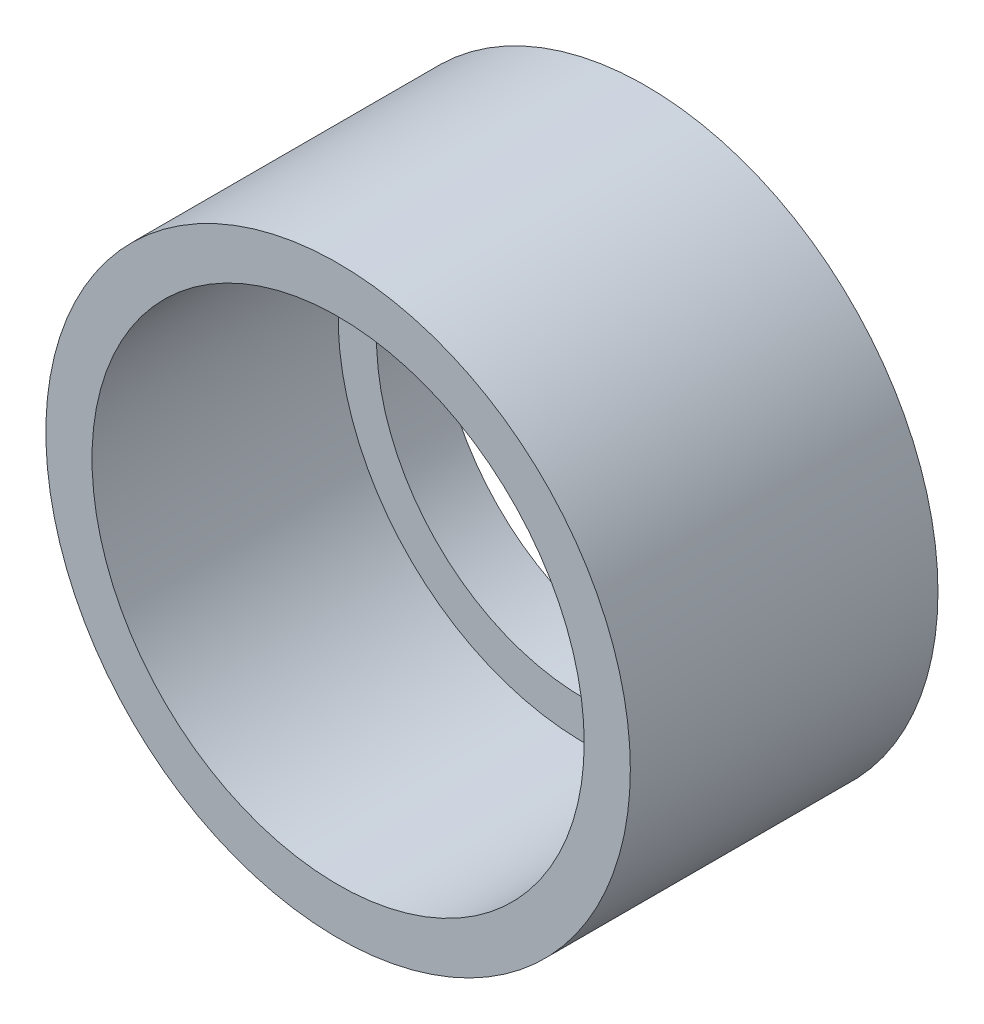
SolidWorks part; units mm, degrees
material "ABS"
ref_plane "Front Plane" through (0, 0, 0) normal (0, 0, 1) x (1, 0, 0)
ref_plane "Top Plane" through (0, 0, 0) normal (0, 1, 0) x (1, 0, 0)
ref_plane "Right Plane" through (0, 0, 0) normal (1, 0, 0) x (0, 0, -1)
sketch "Sketch1" plane through (0, 0, 0) normal (0, 0, 1) x (1, 0, 0)
  circle A0 centre (0, 0) radius 9.5
  circle A1 centre (0, 0) radius 8
  circle A2 centre (0, 0) radius 6.75
  dimension "D1" = 16
  dimension "D2" = 1.5
  dimension "D3" = 13.5
extrude "Boss-Extrude1" add sketch "Sketch1" along normal mid plane 10 contours A0 A1 region at (-9.2313, 0, 0)
extrude "Boss-Extrude2" add sketch "Sketch1<3>" along normal blind 2 from surface contours A1 A2 region at (-7.7737, 0, 0) starting at face at (8, 0, -5)
sketch "Sketch1<3>" plane through (0, 0, 0) normal (0, 0, 1) x (1, 0, 0) same geometry as "Sketch1"
